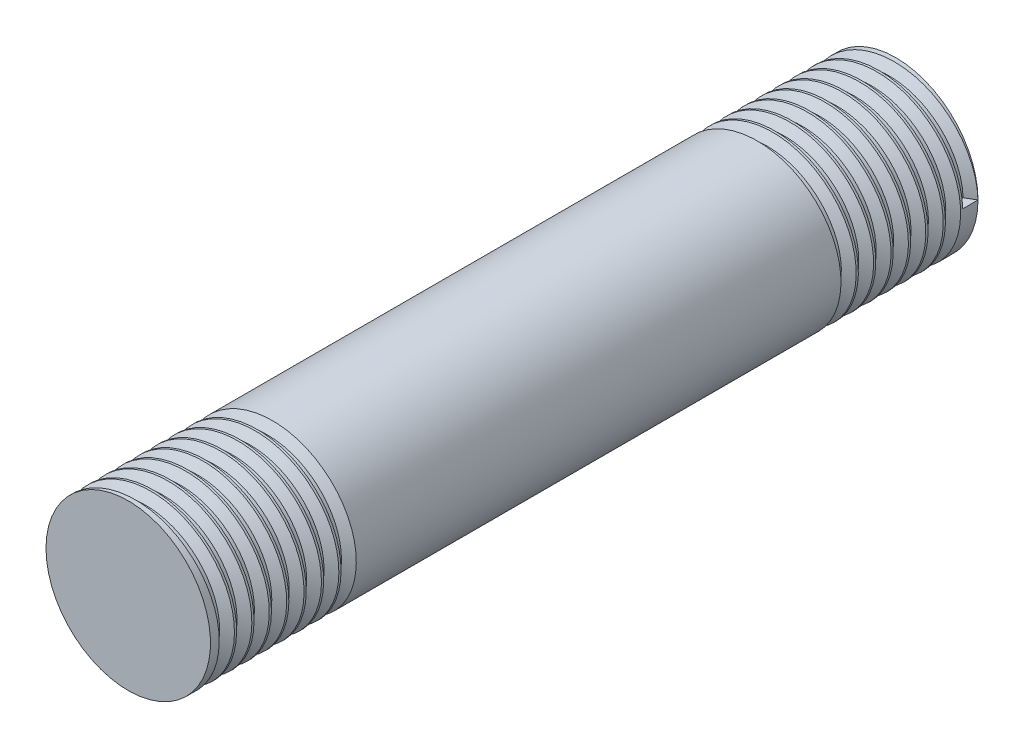
SolidWorks part; units mm, degrees
material "Plain Carbon Steel"
ref_plane "Front Plane" through (0, 0, 0) normal (0, 0, 1) x (1, 0, 0)
ref_plane "Top Plane" through (0, 0, 0) normal (0, 1, 0) x (1, 0, 0)
ref_plane "Right Plane" through (0, 0, 0) normal (1, 0, 0) x (0, 0, -1)
sketch "Sketch1" plane through (0, 0, 0) normal (0, 0, 1) x (1, 0, 0)
  circle A0 centre (0, 0) radius 1.5
  dimension "D1" = 3
extrude "Boss-Extrude1" add sketch "Sketch1" along normal blind 14
thread "Thread1" pitch 0.3175 method cut profile "Thread Profile1" start angle 0, offset 0, length 2.5, pitch 0.3175, diameter 3
ref_plane "Plane1" through (-1.5, 0, 14) normal (0, -1, 0) x (-1, 0, 0)
sketch "Thread Profile1" plane through (-1.5, 0, 14) normal (0, -1, 0) x (-1, 0, 0)
  line L0 (0, 0) -> (0, 0.3175) construction
  line L11 (0, 0) -> (0, 0.2778)
  line L12 (0, 0.2778) -> (-0.1719, 0.1786)
  line L13 (-0.1719, 0.1786) -> (-0.1719, 0.0992)
  line L15 (-0.1719, 0.0992) -> (0, 0)
  line L17 (-0.1719, 0.1389) -> (0, 0.1389) construction
  point P2 (0, 0)
  dimension "Pitch" = 0.3175
  dimension "Profile_Angle" = 60
  dimension "Profile_Land" = 0.0794
  dimension "Profile_Height" = 0.1719
thread "Thread2" pitch 0.3175 method cut profile "Thread Profile2" start angle 0, offset 0, length 2.5, pitch 0.3175, diameter 3
ref_plane "Plane2" through (1.5, 0, 0) normal (0, -1, 0) x (1, 0, 0)
sketch "Thread Profile2" plane through (1.5, 0, 0) normal (0, -1, 0) x (1, 0, 0)
  line L0 (0, 0) -> (0, 0.3175) construction
  line L11 (0, 0) -> (0, 0.2778)
  line L12 (0, 0.2778) -> (-0.1719, 0.1786)
  line L13 (-0.1719, 0.1786) -> (-0.1719, 0.0992)
  line L15 (-0.1719, 0.0992) -> (0, 0)
  line L17 (-0.1719, 0.1389) -> (0, 0.1389) construction
  point P2 (0, 0)
  dimension "Pitch" = 0.3175
  dimension "Profile_Angle" = 60
  dimension "Profile_Land" = 0.0794
  dimension "Profile_Height" = 0.1719
